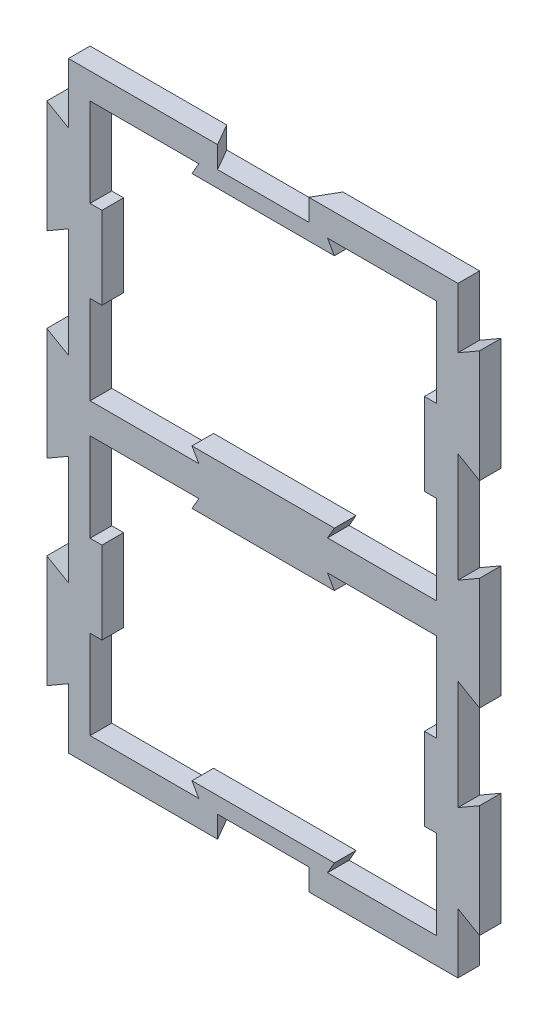
SolidWorks part; units mm, degrees
ref_plane "Front Plane" through (0, 0, 0) normal (1, 0, 0) x (0, 1, 0)
ref_plane "Top Plane" through (0, 0, 0) normal (0, 0, 1) x (0, 1, 0)
ref_plane "Right Plane" through (0, 0, 0) normal (0, 1, 0) x (-1, 0, 0)
sketch "Sketch2" plane through (0, 0, 0) normal (0, 0, 1) x (0, 1, 0)
  line L0 (-55, 0) -> (55, 0) construction
  line L1 (-60, -40) -> (60, -40) construction
  line L2 (-60, -40) -> (-60, 40) construction
  line L3 (-60, 40) -> (60, 40) construction
  line L4 (60, -40) -> (60, 40) construction
  line L5 (-60, -40) -> (60, 40) construction
  line L6 (-60, 40) -> (60, -40) construction
  line L7 (-69.5, -45) -> (69.5, -45)
  line L8 (-69.5, -45) -> (-69.5, 45)
  line L9 (-69.5, 45) -> (69.5, 45)
  line L10 (69.5, -45) -> (69.5, 45)
  line L11 (-69.5, -45) -> (69.5, 45) construction
  line L12 (-69.5, 45) -> (69.5, -45) construction
  line L13 (3.5, -40) -> (63.5, -40)
  line L14 (-63.5, -40) -> (-3.5, -40)
  line L15 (-63.5, -40) -> (-63.5, 40)
  line L16 (-63.5, 40) -> (-3.5, 40)
  line L17 (-3.5, -40) -> (-3.5, 40)
  line L18 (-63.5, -40) -> (-3.5, 40) construction
  line L19 (-63.5, 40) -> (-3.5, -40) construction
  line L20 (3.5, -40) -> (3.5, 40)
  line L21 (3.5, 40) -> (63.5, 40)
  line L22 (63.5, -40) -> (63.5, 40)
  point P0 (0, 0)
  point P6 (0, 0)
  point P15 (-33.5, 0)
  dimension "D5" = 60
  dimension "D1" = 120
  dimension "D2" = 80
  dimension "D3" = 139
  dimension "D4" = 90
  dimension "D6" = 80
  dimension "D7" = 60
  dimension "D8" = 80
  dimension "D9" = 5
  dimension "D10" = 6
  dimension "D11" = 5
  dimension "D12" = 6
extrude "Boss-Extrude1" add sketch "Sketch2" along normal blind 5
sketch "Sketch12" plane through (0, 0, 5) normal (0, 0, 1) x (1, 0, 0)
  line L0 (-50, 32.5192) -> (-50, 58.5)
  line L1 (-50, 58.5) -> (-27.5, 45.5096)
  line L2 (-27.5, 45.5096) -> (-50, 32.5192)
  line L3 (-45, 69.5) -> (-45, -69.5) construction
  line L4 (-27.5, 0) -> (-50, -12.9904)
  line L5 (-50, -12.9904) -> (-50, 12.9904)
  line L6 (-50, 12.9904) -> (-27.5, 0)
  line L7 (-27.5, -45.5096) -> (-50, -58.5)
  line L8 (-50, -58.5) -> (-50, -32.5192)
  line L9 (-50, -32.5192) -> (-27.5, -45.5096)
  line L10 (-45, -69.5) -> (45, -69.5) construction
  line L11 (50, -32.5192) -> (27.5, -45.5096)
  line L12 (50, -58.5) -> (50, -32.5192)
  line L25 (27.5, -45.5096) -> (50, -58.5)
  line L29 (0, -89.25) -> (-16.4545, -60.75)
  line L30 (-16.4545, -60.75) -> (16.4545, -60.75)
  line L31 (16.4545, -60.75) -> (0, -89.25)
  line L32 (-40, -63.5) -> (40, -63.5) construction
  line L39 (50, 12.9904) -> (27.5, 0)
  line L40 (-42, -33.5) -> (42, -33.5) construction
  line L41 (-16.4545, 6.25) -> (16.4545, 6.25)
  line L51 (50, -12.9904) -> (50, 12.9904)
  line L76 (45, -69.5) -> (45, 69.5) construction
  line L77 (-40, -3.5) -> (-40, -63.5) construction
  line L78 (-42.75, -43) -> (-37.25, -43)
  line L79 (-42.75, -43) -> (-42.75, -24)
  line L80 (-42.75, -24) -> (-37.25, -24)
  line L81 (-37.25, -43) -> (-37.25, -24)
  line L82 (-42.75, -43) -> (-37.25, -24) construction
  line L83 (-42.75, -24) -> (-37.25, -43) construction
  line L84 (16.4545, -6.25) -> (0, 22.25)
  line L85 (-16.4545, -6.25) -> (16.4545, -6.25)
  line L86 (0, 22.25) -> (-16.4545, -6.25)
  line L87 (2.75, 0) -> (-2.75, 0) construction
  line L88 (16.4545, 60.75) -> (0, 89.25)
  line L89 (-16.4545, 60.75) -> (16.4545, 60.75)
  line L90 (0, 89.25) -> (-16.4545, 60.75)
  line L94 (0, -2.75) -> (0, 2.75) construction
  line L95 (42.75, -24) -> (37.25, -24)
  line L96 (37.25, -43) -> (37.25, -24)
  line L97 (42.75, -43) -> (37.25, -43)
  line L98 (42.75, -43) -> (42.75, -24)
  line L99 (27.5, 0) -> (50, -12.9904)
  line L100 (42.75, 43) -> (42.75, 24)
  line L101 (42.75, 43) -> (37.25, 43)
  line L102 (37.25, 43) -> (37.25, 24)
  line L103 (42.75, 24) -> (37.25, 24)
  line L104 (-42.75, 24) -> (-37.25, 24)
  line L105 (-37.25, 43) -> (-37.25, 24)
  line L106 (-42.75, 43) -> (-37.25, 43)
  line L107 (-42.75, 43) -> (-42.75, 24)
  line L108 (45, 39.406) -> (45, 59.6132)
  line L109 (27.5, 45.5096) -> (50, 32.5192)
  line L110 (50, 58.5) -> (27.5, 45.5096)
  line L111 (50, 32.5192) -> (50, 58.5)
  line L112 (40, -3.5) -> (-40, -3.5) construction
  line L113 (0, -22.25) -> (-16.4545, 6.25)
  line L114 (16.4545, 6.25) -> (0, -22.25)
  circle A0 centre (-42.5, 45.5096) radius 7.5
  circle A4 centre (0, -70.25) radius 9.5
  circle A5 centre (0, 3.25) radius 9.5
  circle A6 centre (42.5, 45.5096) radius 7.5
  circle A7 centre (0, -3.25) radius 9.5
  point P18 (-40, -33.5)
  line M43 (-45, 69.5) -> (-45, -69.5)
  line M45 (45, -69.5) -> (45, 69.5)
  line M47 (-40, -3.5) -> (40, -3.5)
  line M48 (40, -3.5) -> (40, -63.5)
  line M49 (40, -63.5) -> (-40, -63.5)
  line M50 (-40, -63.5) -> (-40, -3.5)
  line M83 (-40, 63.5) -> (40, 63.5)
  line M84 (40, 63.5) -> (40, 3.5)
  line M85 (40, 3.5) -> (-40, 3.5)
  line M86 (-40, 3.5) -> (-40, 63.5)
  dimension "D1" = 15
  dimension "D6" = 45
  dimension "D8" = 19
  dimension "D2" = 5
  dimension "D4" = 11
  dimension "D5" = 11
  dimension "D7" = 5.5
  dimension "D9" = 19.5289
  dimension "D10" = 19.5289
  dimension "D11" = 2.75
  dimension "D13" = 2.75
  dimension "D12" = 19
  dimension "D3" = 3
sketch "Sketch13" plane through (0, -69.5, -60) normal (0, 1, 0) x (1, 0, 0)
  line L0 (-13.4234, -60) -> (13.4234, -60)
  line L1 (13.4234, -60) -> (0, -83.25)
  line L2 (0, -83.25) -> (-13.4234, -60)
  line L3 (0, -115) -> (0, -5) construction
  line L4 (-45, -65) -> (45, -65) construction
  circle A0 centre (0, -67.75) radius 7.75
  dimension "D1" = 15.5
  dimension "D2" = 5
extrude "Cut-Extrude5" cut sketch "Sketch13" along normal blind 5 contours L1 L2 L0
extrude "Cut-Extrude6" cut sketch "Sketch13<3>" along normal blind 5 from offset 134 contours L0 L1 L2
sketch "Sketch13<3>" plane through (0, -69.5, -60) normal (0, 1, 0) x (1, 0, 0) same geometry as "Sketch13"
extrude "Boss-Extrude2" add sketch "Sketch12" against normal up to surface (5 mm away) contours L90 L89 L88 M83 | A0 L0 L2 M43 | A0 M43 | A0 L1 L0 M43 | A6 M45 | L108 A6 L111 L110 | L111 A6 L109 M45 | L109 L102 L103 M84 | A6 L101 L102 M84 | L109 A6 L102 | A6 L109 M84 | A0 L107 L2 M86 | A0 L2 M86 | A0 L2 L105 | L105 L2 L104 M86 | A0 L105 L106 M86 | L85 L113 L86 M47 | A7 L113 L85 M47 | A7 L85 A5 M47 | A5 M47 | L85 A7 A5 M47 | A7 L85 L114 M47 | L114 L85 L84 M47 | L114 L41 L84 M85 | L41 A5 L84 M85 | A7 A5 L41 M85 | A7 M85 | A7 L41 A5 M85 | L113 L86 L41 M85 | A5 L41 L86 M85 | L6 L5 L4 M43 | L99 L51 L39 M45 | L96 L11 L95 M48 | L97 L11 L96 M48 | L25 L12 L11 M45 | L9 L8 L7 M43 | L9 L81 L80 M50 | L78 L81 L9 M50 | A4 L30 L29 M49 | A4 M49 | A4 L31 L30 M49 region at (-48.0343, 37.3053, 5) region at (-48.0343, 53.7139, 5) region at (-47.0711, 45.5096, 5) region at (-41.793, 37.667, 5) region at (-47.6042, 0, 5) region at (-39.6832, 38.5197, 5) region at (-38.6009, 31.5503, 5) region at (-38.7259, 41.0467, 5) region at (-37.615, 39.7503, 5) region at (-47.6042, -45.5096, 5) region at (-12.846, 5.0043, 5) region at (-38.6009, -31.5503, 5) region at (0, 62.1018, 5) region at (-9.8127, 4.5158, 5) region at (-12.846, -5.0043, 5) region at (-38.718, -41.0165, 5) region at (-9.8127, -4.5158, 5) region at (-6.7117, 5.1053, 5) region at (-6.7117, -5.1053, 5) region at (0, 4.6149, 5) region at (-10.0329, -61.9838, 5) region at (0, -4.6149, 5) region at (6.7117, 5.1053, 5) region at (0, -62.3851, 5) region at (48.0343, 53.7139, 5) region at (6.7117, -5.1053, 5) region at (9.8127, 4.5158, 5) region at (12.846, 5.0043, 5) region at (10.0329, -61.9838, 5) region at (47.0711, 45.5096, 5) region at (37.615, 39.7503, 5) region at (38.7259, 41.0467, 5) region at (9.8127, -4.5158, 5) region at (12.846, -5.0043, 5) region at (48.0343, 37.3053, 5) region at (38.6009, 31.5503, 5) region at (39.6832, 38.5197, 5) region at (47.6042, -45.5096, 5) region at (38.718, -41.0165, 5) region at (47.6042, 0, 5) region at (38.6009, -31.5503, 5) up to plane "Top Plane"
